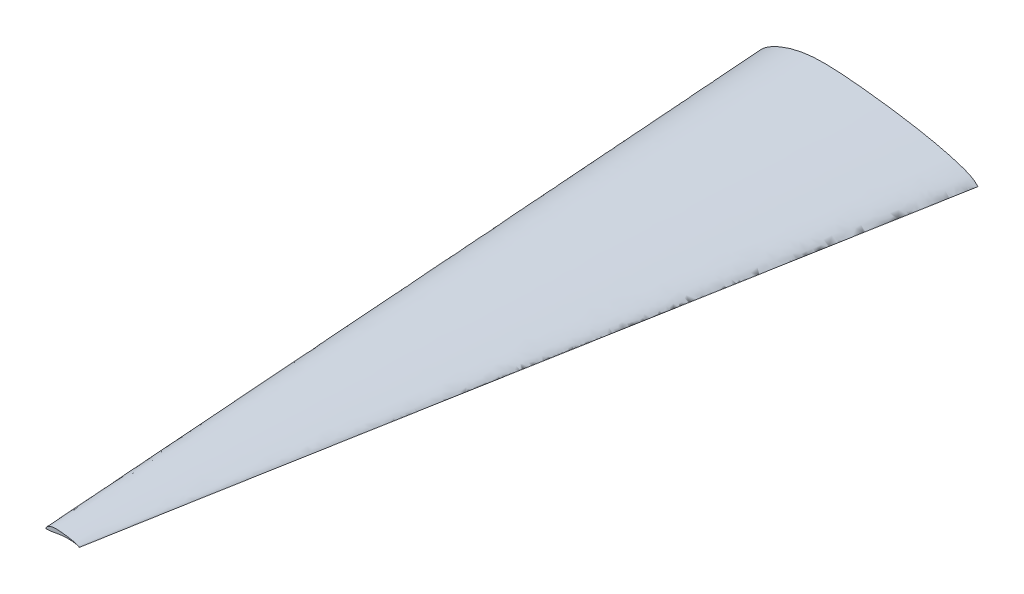
SolidWorks part; units mm, degrees
ref_plane "Front Plane" through (0, 0, 0) normal (0, 0, 1) x (1, 0, 0)
ref_plane "Top Plane" through (0, 0, 0) normal (0, 1, 0) x (1, 0, 0)
ref_plane "Right Plane" through (0, 0, 0) normal (1, 0, 0) x (0, 0, -1)
curve "Curve1"
  spline degree 3 poles (99.6236, 0.2734, 0) (100.0885, -0.0674, 0) (99.6804, 0.2552, 0) (99.3896, 0.5119, 0) (98.7854, 1.0963, 0) (98.0525, 1.7008, 0) (97.051, 2.3064, 0) (95.8088, 2.8928, 0) (94.3195, 3.525, 0) (92.568, 4.1565, 0) (90.5717, 4.8004, 0) (88.342, 5.4609, 0) (85.8862, 6.1142, 0) (83.22, 6.7747, 0) (80.3581, 7.4187, 0) (77.3208, 8.0567, 0) (74.1245, 8.687, 0) (70.7875, 9.2937, 0) (67.3304, 9.8733, 0) (63.7754, 10.4173, 0) (60.1467, 10.9506, 0) (56.4595, 11.4396, 0) (52.7481, 11.8821, 0) (49.0388, 12.3062, 0) (45.3653, 12.6836, 0) (41.7526, 13.0186, 0) (38.2323, 13.278, 0) (34.8219, 13.466, 0) (31.5405, 13.543, 0) (28.4013, 13.5372, 0) (25.4135, 13.3807, 0) (22.5756, 13.073, 0) (19.8811, 12.6168, 0) (17.3167, 12.061, 0) (14.8938, 11.3939, 0) (12.6231, 10.6323, 0) (10.5152, 9.8084, 0) (8.5797, 8.9174, 0) (6.8248, 7.9803, 0) (5.2478, 7.0223, 0) (3.8908, 6.0117, 0) (2.7072, 5.0327, 0) (1.7679, 4.0079, 0) (1.0321, 3.0012, 0) (0.4921, 2.0154, 0) (0.147, 1.0822, 0) (-0.0148, 0.2204, 0) (0.0021, -0.509, 0) (0.1935, -1.1802, 0) (0.8937, -1.5142, 0) (1.8361, -1.5573, 0) (3.1206, -1.5967, 0) (4.7349, -1.5333, 0) (6.6618, -1.3994, 0) (8.8787, -1.1971, 0) (11.3678, -0.9329, 0) (14.1082, -0.5566, 0) (17.1122, -0.0837, 0) (20.3748, 0.5668, 0) (23.9308, 1.2222, 0) (27.7486, 1.9561, 0) (31.8167, 2.666, 0) (36.0968, 3.3849, 0) (40.5615, 4.0371, 0) (45.1672, 4.6408, 0) (49.8744, 5.1515, 0) (54.6395, 5.5473, 0) (59.4136, 5.84, 0) (64.1453, 6.0062, 0) (68.7841, 6.0102, 0) (73.2798, 5.8984, 0) (77.5824, 5.6404, 0) (81.6385, 5.2556, 0) (85.3995, 4.754, 0) (88.8146, 4.1381, 0) (91.8474, 3.453, 0) (94.4337, 2.6976, 0) (96.5532, 1.9066, 0) (98.0744, 1.195, 0) (99.1818, 0.512, 0) (99.6236, 0.2734, 0) (100.0885, -0.0674, 0) (99.6804, 0.2552, 0) knots -0.009729 -0.004146 -0.000993 0 0.000984 0.003625 0.007475 0.01209 0.017534 0.024067 0.031789 0.040683 0.050722 0.061823 0.073981 0.08711 0.101156 0.115986 0.131554 0.147808 0.164554 0.181749 0.199308 0.217076 0.235011 0.252833 0.27054 0.287892 0.304788 0.321088 0.336797 0.351786 0.366031 0.379621 0.39264 0.405149 0.417181 0.428608 0.439431 0.449576 0.459101 0.46791 0.475968 0.483315 0.489868 0.495817 0.501135 0.505907 0.510027 0.513562 0.516434 0.519365 0.523841 0.530001 0.537737 0.546971 0.557658 0.569614 0.582812 0.597267 0.613154 0.630446 0.649049 0.668825 0.689582 0.711198 0.733436 0.756098 0.778995 0.801901 0.824588 0.846785 0.86832 0.888979 0.908496 0.926656 0.943294 0.958185 0.971129 0.981945 0.990271 0.995854 0.999007 1 1.000984 1.003625 1.007475 periodic
sketch "Sketch2" plane through (0, 0, 0) normal (0, 0, 1) x (1, 0, 0)
  spline S1 degree 3 poles (199.2471, 0.5468) (200.177, -0.1348) (199.3608, 0.5104) (198.7792, 1.0238) (197.5708, 2.1925) (196.1051, 3.4016) (194.1019, 4.6128) (191.6177, 5.7855) (188.639, 7.05) (185.136, 8.313) (181.1434, 9.6009) (176.6841, 10.9219) (171.7724, 12.2284) (166.4399, 13.5494) (160.7162, 14.8373) (154.6415, 16.1135) (148.249, 17.3741) (141.575, 18.5874) (134.6608, 19.7466) (127.5509, 20.8347) (120.2934, 21.9013) (112.9191, 22.8792) (105.4962, 23.7642) (98.0776, 24.6124) (90.7306, 25.3672) (83.5053, 26.0373) (76.4645, 26.556) (69.6438, 26.9321) (63.081, 27.0861) (56.8027, 27.0744) (50.8271, 26.7613) (45.1512, 26.1459) (39.7622, 25.2335) (34.6335, 24.1219) (29.7876, 22.7877) (25.2463, 21.2646) (21.0304, 19.6168) (17.1594, 17.8348) (13.6497, 15.9607) (10.4956, 14.0446) (7.7817, 12.0233) (5.4144, 10.0655) (3.5358, 8.0159) (2.0642, 6.0025) (0.9842, 4.0308) (0.2939, 2.1644) (-0.0296, 0.4409) (0.0041, -1.018) (0.3871, -2.3604) (1.7874, -3.0284) (3.6722, -3.1146) (6.2412, -3.1935) (9.4698, -3.0666) (13.3237, -2.7988) (17.7573, -2.3943) (22.7355, -1.8659) (28.2164, -1.1133) (34.2245, -0.1674) (40.7497, 1.1335) (47.8616, 2.4445) (55.4971, 3.9122) (63.6334, 5.3319) (72.1936, 6.7699) (81.1231, 8.0743) (90.3344, 9.2817) (99.7489, 10.303) (109.2789, 11.0946) (118.8272, 11.6801) (128.2906, 12.0124) (137.5682, 12.0204) (146.5597, 11.7968) (155.1648, 11.2809) (163.2771, 10.5113) (170.799, 9.508) (177.6292, 8.2762) (183.6948, 6.9059) (188.8673, 5.3952) (193.1065, 3.8132) (196.1488, 2.3901) (198.3636, 1.0239) (199.2471, 0.5468) (200.177, -0.1348) (199.3608, 0.5104) knots -0.009729 -0.004146 -0.000993 0 0.000984 0.003625 0.007475 0.01209 0.017534 0.024067 0.031789 0.040683 0.050722 0.061823 0.073981 0.08711 0.101156 0.115986 0.131554 0.147808 0.164554 0.181749 0.199308 0.217076 0.235011 0.252833 0.27054 0.287892 0.304788 0.321088 0.336797 0.351786 0.366031 0.379621 0.39264 0.405149 0.417181 0.428608 0.439431 0.449576 0.459101 0.46791 0.475968 0.483315 0.489868 0.495817 0.501135 0.505907 0.510027 0.513562 0.516434 0.519365 0.523841 0.530001 0.537737 0.546971 0.557658 0.569614 0.582812 0.597267 0.613154 0.630446 0.649049 0.668825 0.689582 0.711198 0.733436 0.756098 0.778995 0.801901 0.824588 0.846785 0.86832 0.888979 0.908496 0.926656 0.943294 0.958185 0.971129 0.981945 0.990271 0.995854 0.999007 1 1.000984 1.003625 1.007475 only from (200, 0) to (200, 0)
ref_plane "Plane1" through (0, 0, 700) normal (0, 0, 1) x (1, 0, 0)
sketch "Sketch3" plane through (0, 0, 700) normal (0, 0, 1) x (1, 0, 0)
  spline S1 degree 3 poles (91.1001, 14.4751) (91.2396, 14.3729) (91.1172, 14.4697) (91.0299, 14.5467) (90.8487, 14.722) (90.6288, 14.9034) (90.3283, 15.085) (89.9557, 15.2609) (89.5089, 15.4506) (88.9834, 15.6401) (88.3846, 15.8332) (87.7156, 16.0314) (86.9789, 16.2274) (86.179, 16.4255) (85.3205, 16.6187) (84.4093, 16.8101) (83.4504, 16.9992) (82.4493, 17.1812) (81.4122, 17.3551) (80.3457, 17.5183) (79.257, 17.6783) (78.1509, 17.825) (77.0375, 17.9577) (75.9247, 18.085) (74.8226, 18.1982) (73.7388, 18.2987) (72.6827, 18.3765) (71.6596, 18.4329) (70.6752, 18.456) (69.7334, 18.4543) (68.8371, 18.4073) (67.9857, 18.315) (67.1774, 18.1781) (66.4081, 18.0114) (65.6812, 17.8113) (65, 17.5828) (64.3676, 17.3356) (63.7869, 17.0683) (63.2605, 16.7872) (62.7874, 16.4998) (62.3803, 16.1966) (62.0252, 15.9029) (61.7434, 15.5955) (61.5227, 15.2935) (61.3607, 14.9977) (61.2571, 14.7178) (61.2086, 14.4592) (61.2137, 14.2404) (61.2711, 14.039) (61.4811, 13.9388) (61.7639, 13.9259) (62.1492, 13.9141) (62.6335, 13.9331) (63.2116, 13.9733) (63.8766, 14.034) (64.6234, 14.1132) (65.4455, 14.2261) (66.3467, 14.368) (67.3255, 14.5631) (68.3923, 14.7598) (69.5376, 14.9799) (70.758, 15.1929) (72.0421, 15.4086) (73.3815, 15.6042) (74.7632, 15.7854) (76.1754, 15.9386) (77.6049, 16.0573) (79.0371, 16.1451) (80.4566, 16.195) (81.8483, 16.1962) (83.197, 16.1626) (84.4878, 16.0852) (85.7046, 15.9698) (86.8329, 15.8193) (87.8574, 15.6345) (88.7673, 15.429) (89.5431, 15.2024) (90.179, 14.9651) (90.6354, 14.7516) (90.9676, 14.5467) (91.1001, 14.4751) (91.2396, 14.3729) (91.1172, 14.4697) knots -0.009729 -0.004146 -0.000993 0 0.000984 0.003625 0.007475 0.01209 0.017534 0.024067 0.031789 0.040683 0.050722 0.061823 0.073981 0.08711 0.101156 0.115986 0.131554 0.147808 0.164554 0.181749 0.199308 0.217076 0.235011 0.252833 0.27054 0.287892 0.304788 0.321088 0.336797 0.351786 0.366031 0.379621 0.39264 0.405149 0.417181 0.428608 0.439431 0.449576 0.459101 0.46791 0.475968 0.483315 0.489868 0.495817 0.501135 0.505907 0.510027 0.513562 0.516434 0.519365 0.523841 0.530001 0.537737 0.546971 0.557658 0.569614 0.582812 0.597267 0.613154 0.630446 0.649049 0.668825 0.689582 0.711198 0.733436 0.756098 0.778995 0.801901 0.824588 0.846785 0.86832 0.888979 0.908496 0.926656 0.943294 0.958185 0.971129 0.981945 0.990271 0.995854 0.999007 1 1.000984 1.003625 1.007475 only from (91.213, 14.3931) to (91.213, 14.3931)
loft "Loft1" add profiles "Sketch2", "Sketch3" connector at (0.3656, -2.0157, 0) connector at (61.2193, 14.2645, 700)
